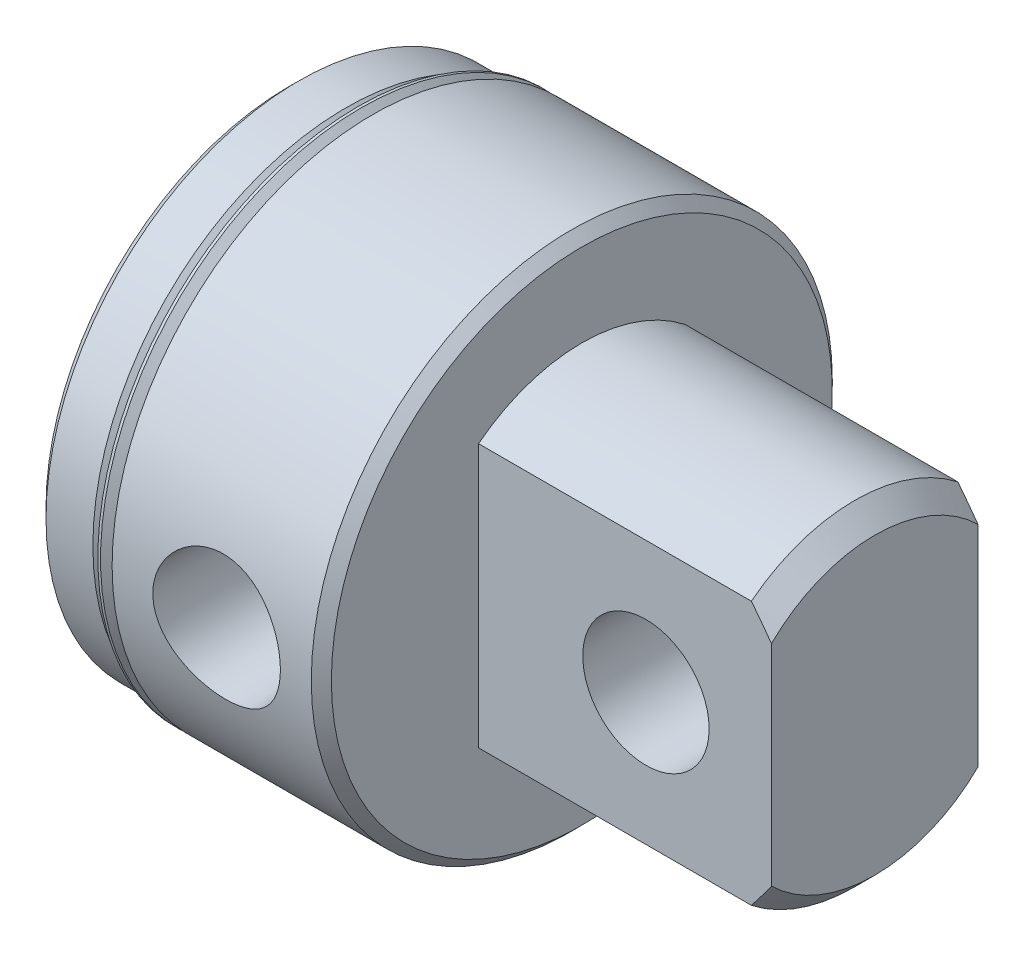
SolidWorks part; units mm, degrees
material "Plain Carbon Steel"
ref_plane "Front Plane" through (0, 0, 0) normal (0, 0, 1) x (1, 0, 0)
ref_plane "Top Plane" through (0, 0, 0) normal (0, 1, 0) x (1, 0, 0)
ref_plane "Right Plane" through (0, 0, 0) normal (1, 0, 0) x (0, 0, -1)
ref_plane "Plane1" through (44.45, 0, 0) normal (1, 0, 0) x (0, 0, -1)
sketch "Sketch1" plane through (0, 0, 0) normal (0, 0, 1) x (1, 0, 0)
  line L0 (0, 0) -> (0, 18.434)
  line L1 (0, 18.434) -> (0.762, 19.196)
  line L2 (0.762, 19.196) -> (4.318, 19.196)
  line L3 (4.318, 19.196) -> (5.334, 18.1801)
  line L4 (5.334, 18.1801) -> (6.35, 18.1801)
  line L5 (6.35, 18.1801) -> (6.35, 19.7676)
  line L6 (6.35, 19.7676) -> (21.463, 19.7676)
  line L7 (21.463, 19.7676) -> (22.225, 19.0055)
  line L8 (22.225, 19.0055) -> (22.225, 0)
  line L9 (22.225, 0) -> (0, 0)
  line L10 (22.225, 0) -> (0, 0) construction
revolve "Revolve1" add sketch "Sketch1" angle 360 about L10 reverse direction yes
sketch "Sketch2" plane through (0, 0, 0) normal (0, 0, 1) x (1, 0, 0)
  line L0 (22.225, 0) -> (22.225, 12.7)
  line L1 (22.225, 12.7) -> (42.926, 12.7)
  line L2 (42.926, 12.7) -> (44.45, 11.176)
  line L3 (44.45, 11.176) -> (44.45, 0)
  line L4 (44.45, 0) -> (22.225, 0)
  line L5 (44.45, 0) -> (22.225, 0) construction
revolve "Revolve2" add sketch "Sketch2" angle 360 about L5 reverse direction yes
sketch "Sketch3" plane through (44.45, 0, 0) normal (1, 0, 0) x (0, 0, -1)
  line L0 (-39.5351, -79.0702) -> (39.5351, -79.0702)
  line L1 (39.5351, -79.0702) -> (39.5351, 79.0702)
  line L2 (39.5351, 79.0702) -> (-39.5351, 79.0702)
  line L3 (-39.5351, 79.0702) -> (-39.5351, -79.0702)
  line L4 (-7.8359, -39.5351) -> (7.8359, -39.5351)
  line L5 (7.8359, -39.5351) -> (7.8359, 39.5351)
  line L6 (7.8359, 39.5351) -> (-7.8359, 39.5351)
  line L7 (-7.8359, 39.5351) -> (-7.8359, -39.5351)
extrude "Cut-Extrude1" cut sketch "Sketch3" against normal blind 22.225
ref_plane "Plane2" through (22.225, 0, 0) normal (1, 0, 0) x (0, 0, -1)
hole_wizard "Hole1" positions "Sketch5" profile "Sketch4" legacy
sketch "Sketch5" plane through (0, 0, 0) normal (-1, 0, 0) x (0, 0, 1)
  point P0 (0, 0)
sketch "Sketch4" plane through (0, 0, 0) normal (0, 1, 0) x (0, 0, 1)
  line L0 (0, 0) -> (0, 24.3529)
  line L1 (0, 24.3529) -> (6.7564, 20.4521)
  line L2 (6.7564, 20.4521) -> (6.7564, 0)
  line L4 (6.7564, 0) -> (0, 0)
  line L6 (0, 24.3529) -> (-6.7564, 20.4521) construction
  line L7 (0, -4.2442) -> (0, 117.3081) construction
  dimension "Diameter" = 13.5128
  dimension "Depth" = 20.4521
  dimension "Drill Angle" = 120
ref_plane "Plane3" through (0, 0, 0) normal (0, 0.9998, 0.0175) x (1, 0, 0)
sketch "Sketch6" plane through (0, 0, 0) normal (0, 0.9998, 0.0175) x (1, 0, 0)
  line L0 (14.2748, 0) -> (18.8978, 0)
  line L1 (18.8978, 0) -> (18.8978, -12.8333)
  line L2 (18.8978, -12.8333) -> (19.1143, -19.7675)
  line L3 (19.1143, -19.7675) -> (14.2748, -19.7675)
  line L4 (14.2748, -19.7675) -> (14.2748, 0)
  line L5 (14.2748, -19.7675) -> (14.2748, 0) construction
revolve "Cut-Revolve1" cut sketch "Sketch6" angle 360 about L5 reverse direction yes
cosmetic thread "Cosmetic Thread1" parameters "D1"=6.9342, "D2"=10.287
ref_plane "Plane4" through (14.2748, 0, 0) normal (1, 0, 0) x (0, 0, -1)
sketch "Sketch7" plane through (0, 0, 0) normal (0, 0, 1) x (1, 0, 0)
  line L0 (0, 0) -> (0, 12.3063)
  line L1 (0, 12.3063) -> (6.35, 12.3063)
  line L2 (6.35, 12.3063) -> (6.35, 0)
  line L3 (6.35, 0) -> (0, 0)
  line L4 (6.35, 0) -> (0, 0) construction
revolve "Cut-Revolve2" cut sketch "Sketch7" angle 360 about L4 reverse direction yes
ref_plane "Plane5" through (5.334, 0, 0) normal (1, 0, 0) x (0, 0, -1)
sketch "Sketch8" plane through (0, 0, 0) normal (0, 0, 1) x (1, 0, 0)
  line L0 (5.2675, 19.6834) -> (6.2166, 18.7343)
  line L1 (6.2166, 18.5547) -> (5.842, 18.1801)
  line L2 (5.842, 18.1801) -> (5.334, 18.1801)
  line L3 (5.334, 18.1801) -> (5.334, 17.9261)
  line L4 (5.334, 17.9261) -> (6.35, 17.9261)
  line L5 (6.35, 17.9261) -> (6.35, 18.8883)
  line L6 (6.35, 18.8883) -> (5.4707, 19.7676)
  line L7 (5.4707, 19.7676) -> (5.2675, 19.7676)
  line L8 (5.2675, 19.7676) -> (5.2675, 19.6834)
  line L9 (6.35, 0) -> (5.334, 0) construction
  arc A0 (6.2166, 18.7343) -> (6.2166, 18.5547) centre (6.1268, 18.6445) cw
revolve "Revolve3" add sketch "Sketch8" angle 360 about L9 reverse direction yes
ref_plane "Plane6" through (44.577, 0, 0) normal (1, 0, 0) x (0, 0, -1)
sketch "Sketch9" plane through (0, 0, 0) normal (0, 0, 1) x (1, 0, 0)
  circle A0 centre (34.925, 0) radius 4.7942
extrude "Cut-Extrude2" cut sketch "Sketch9" along normal blind 11.7538 and the other way blind 11.7538
ref_plane "Plane7" through (0, 0, 0) normal (1, 0, 0) x (0, 0, -1)
ref_plane "Plane8" through (38.1, 0, 0) normal (1, 0, 0) x (0, 0, -1)
ref_plane "Plane9" through (34.925, 0, 0) normal (1, 0, 0) x (0, 0, -1)
ref_plane "Plane10" through (44.45, 0, 0) normal (1, 0, 0) x (0, 0, -1)
ref_plane "Plane11" through (0, 0, 0) normal (0, 0, 1) x (1, 0, 0)
ref_plane "Plane12" through (0, 0, 0) normal (0, 1, 0) x (1, 0, 0)
ref_plane "Plane13" through (0, 14.2875, 0) normal (0, 1, 0) x (1, 0, 0)
ref_plane "Plane14" through (0, 0, 0) normal (0, 0, 1) x (1, 0, 0)
ref_plane "Plane15" through (22.225, 0, 0) normal (1, 0, 0) x (0, 0, -1)
ref_plane "f XY" through (0, 0, 0) normal (0, 0, 1) x (1, 0, 0)
ref_plane "f XZ" through (0, 0, 0) normal (0, -1, 0) x (-1, 0, 0)
ref_plane "f YZ" through (22.225, 0, 0) normal (1, 0, 0) x (0, 0, -1)
ref_axis "f X" through (-80.9, 0, 0) along (1, 0, 0)
ref_axis "f Y" through (22.225, -50, 0) along (0, 1, 0)
ref_axis "f Z" through (22.225, 0, 80.9) along (0, 0, -1)
sketch3d "f"
  point P0 (22.225, 0, 0)
ref_plane "lovra1 XY" through (38.1, 0, 0) normal (1, 0, 0) x (0, 0, -1)
ref_plane "lovra1 XZ" through (0, 0, 0) normal (0, -1, 0) x (-1, 0, 0)
ref_plane "lovra1 YZ" through (0, 0, 0) normal (0, 0, -1) x (-1, 0, 0)
ref_axis "lovra1 X" through (38.1, 0, 80.9) along (0, 0, -1)
ref_axis "lovra1 Y" through (38.1, -50, 0) along (0, 1, 0)
ref_axis "lovra1 Z" through (80.9, 0, 0) along (-1, 0, 0)
sketch3d "lovra1"
  point P0 (38.1, 0, 0)
ref_plane "lovra2 XY" through (38.1, 0, 0) normal (1, 0, 0) x (0, 0, -1)
ref_plane "lovra2 XZ" through (0, 11.049, 0) normal (0, -1, 0) x (-1, 0, 0)
ref_plane "lovra2 YZ" through (0, 0, 0) normal (0, 0, -1) x (-1, 0, 0)
ref_axis "lovra2 X" through (38.1, 11.049, 80.9) along (0, 0, -1)
ref_axis "lovra2 Y" through (38.1, -50, 0) along (0, 1, 0)
ref_axis "lovra2 Z" through (80.9, 11.049, 0) along (-1, 0, 0)
sketch3d "lovra2"
  point P0 (38.1, 11.049, 0)
ref_plane "lovra21 XY" through (0, 0, 0) normal (1, 0, 0) x (0, 0, -1)
ref_plane "lovra21 XZ" through (0, 0, 0) normal (0, -1, 0) x (-1, 0, 0)
ref_plane "lovra21 YZ" through (0, 0, 5.2705) normal (0, 0, -1) x (-1, 0, 0)
ref_axis "lovra21 X" through (0, 0, 80.9) along (0, 0, -1)
ref_axis "lovra21 Y" through (0, -50, 5.2705) along (0, 1, 0)
ref_axis "lovra21 Z" through (80.9, 0, 5.2705) along (-1, 0, 0)
sketch3d "lovra21"
  point P0 (0, 0, 5.2705)
ref_plane "lovra22 XY" through (0, 0, 0) normal (1, 0, 0) x (0, 0, -1)
ref_plane "lovra22 XZ" through (0, 0, 0) normal (0, -1, 0) x (-1, 0, 0)
ref_plane "lovra22 YZ" through (0, 0, -5.2705) normal (0, 0, -1) x (-1, 0, 0)
ref_axis "lovra22 X" through (0, 0, 80.9) along (0, 0, -1)
ref_axis "lovra22 Y" through (0, -50, -5.2705) along (0, 1, 0)
ref_axis "lovra22 Z" through (80.9, 0, -5.2705) along (-1, 0, 0)
sketch3d "lovra22"
  point P0 (0, 0, -5.2705)
ref_plane "lovra3 XY" through (38.1, 0, 0) normal (1, 0, 0) x (0, 0, -1)
ref_plane "lovra3 XZ" through (0, -11.049, 0) normal (0, -1, 0) x (-1, 0, 0)
ref_plane "lovra3 YZ" through (0, 0, 0) normal (0, 0, -1) x (-1, 0, 0)
ref_axis "lovra3 X" through (38.1, -11.049, 80.9) along (0, 0, -1)
ref_axis "lovra3 Y" through (38.1, -50, 0) along (0, 1, 0)
ref_axis "lovra3 Z" through (80.9, -11.049, 0) along (-1, 0, 0)
sketch3d "lovra3"
  point P0 (38.1, -11.049, 0)
ref_plane "olen XY" through (34.925, 0, 0) normal (1, 0, 0) x (0, 0, -1)
ref_plane "olen XZ" through (0, 0, 0) normal (0, -1, 0) x (-1, 0, 0)
ref_plane "olen YZ" through (0, 0, 0) normal (0, 0, -1) x (-1, 0, 0)
ref_axis "olen X" through (34.925, 0, 80.9) along (0, 0, -1)
ref_axis "olen Y" through (34.925, -50, 0) along (0, 1, 0)
ref_axis "olen Z" through (80.9, 0, 0) along (-1, 0, 0)
sketch3d "olen"
  point P0 (34.925, 0, 0)
ref_plane "p1 XY" through (44.45, 0, 0) normal (1, 0, 0) x (0, 0, -1)
ref_plane "p1 XZ" through (0, 0, 0) normal (0, -1, 0) x (-1, 0, 0)
ref_plane "p1 YZ" through (0, 0, 7.8359) normal (0, 0, -1) x (-1, 0, 0)
ref_axis "p1 X" through (44.45, 0, 80.9) along (0, 0, -1)
ref_axis "p1 Y" through (44.45, -50, 7.8359) along (0, 1, 0)
ref_axis "p1 Z" through (80.9, 0, 7.8359) along (-1, 0, 0)
sketch3d "p1"
  point P0 (44.45, 0, 7.8359)
ref_plane "p2 XY" through (44.45, 0, 0) normal (1, 0, 0) x (0, 0, -1)
ref_plane "p2 XZ" through (0, 0, 0) normal (0, -1, 0) x (-1, 0, 0)
ref_plane "p2 YZ" through (0, 0, -7.8359) normal (0, 0, -1) x (-1, 0, 0)
ref_axis "p2 X" through (44.45, 0, 80.9) along (0, 0, -1)
ref_axis "p2 Y" through (44.45, -50, -7.8359) along (0, 1, 0)
ref_axis "p2 Z" through (80.9, 0, -7.8359) along (-1, 0, 0)
sketch3d "p2"
  point P0 (44.45, 0, -7.8359)
ref_plane "port XY" through (0, 0, 0) normal (0, 0, 1) x (1, 0, 0)
ref_plane "port XZ" through (0, 0, 0) normal (0, -1, 0) x (-1, 0, 0)
ref_plane "port YZ" through (14.2748, 0, 0) normal (1, 0, 0) x (0, 0, -1)
ref_axis "port X" through (-80.9, 0, 0) along (1, 0, 0)
ref_axis "port Y" through (14.2748, -50, 0) along (0, 1, 0)
ref_axis "port Z" through (14.2748, 0, 80.9) along (0, 0, -1)
sketch3d "port"
  point P0 (14.2748, 0, 0)
ref_plane "port2 XY" through (44.45, 0, 0) normal (1, 0, 0) x (0, 0, -1)
ref_plane "port2 XZ" through (0, 0, 0) normal (0, -1, 0) x (-1, 0, 0)
ref_plane "port2 YZ" through (0, 0, 0) normal (0, 0, -1) x (-1, 0, 0)
ref_axis "port2 X" through (44.45, 0, 80.9) along (0, 0, -1)
ref_axis "port2 Y" through (44.45, -50, 0) along (0, 1, 0)
ref_axis "port2 Z" through (80.9, 0, 0) along (-1, 0, 0)
sketch3d "port2"
  point P0 (44.45, 0, 0)
ref_plane "thd1 XY" through (44.45, 0, 0) normal (1, 0, 0) x (0, 0, -1)
ref_plane "thd1 XZ" through (0, 0, 0) normal (0, -1, 0) x (-1, 0, 0)
ref_plane "thd1 YZ" through (0, 0, 0) normal (0, 0, -1) x (-1, 0, 0)
ref_axis "thd1 X" through (44.45, 0, 80.9) along (0, 0, -1)
ref_axis "thd1 Y" through (44.45, -50, 0) along (0, 1, 0)
ref_axis "thd1 Z" through (80.9, 0, 0) along (-1, 0, 0)
sketch3d "thd1"
  point P0 (44.45, 0, 0)
ref_plane "thd2 XY" through (44.45, 0, 0) normal (1, 0, 0) x (0, 0, -1)
ref_plane "thd2 XZ" through (0, 0, 0) normal (0, -1, 0) x (-1, 0, 0)
ref_plane "thd2 YZ" through (0, 0, 0) normal (0, 0, -1) x (-1, 0, 0)
ref_axis "thd2 X" through (44.45, 0, 80.9) along (0, 0, -1)
ref_axis "thd2 Y" through (44.45, -50, 0) along (0, 1, 0)
ref_axis "thd2 Z" through (80.9, 0, 0) along (-1, 0, 0)
sketch3d "thd2"
  point P0 (44.45, 0, 0)
ref_plane "to_mounting_bracket XY" through (22.225, 0, 0) normal (1, 0, 0) x (0, 0, -1)
ref_plane "to_mounting_bracket XZ" through (0, 0, 0) normal (0, -1, 0) x (-1, 0, 0)
ref_plane "to_mounting_bracket YZ" through (0, 0, 0) normal (0, 0, -1) x (-1, 0, 0)
ref_axis "to_mounting_bracket X" through (22.225, 0, 80.9) along (0, 0, -1)
ref_axis "to_mounting_bracket Y" through (22.225, -50, 0) along (0, 1, 0)
ref_axis "to_mounting_bracket Z" through (80.9, 0, 0) along (-1, 0, 0)
sketch3d "to_mounting_bracket"
  point P0 (22.225, 0, 0)
ref_plane "to_nut XY" through (0, 0, 0) normal (1, 0, 0) x (0, 0, -1)
ref_plane "to_nut XZ" through (0, 0, 0) normal (0, -1, 0) x (-1, 0, 0)
ref_plane "to_nut YZ" through (0, 0, 0) normal (0, 0, -1) x (-1, 0, 0)
ref_axis "to_nut X" through (0, 0, 80.9) along (0, 0, -1)
ref_axis "to_nut Y" through (0, -50, 0) along (0, 1, 0)
ref_axis "to_nut Z" through (80.9, 0, 0) along (-1, 0, 0)
sketch3d "to_nut"
  point P0 (0, 0, 0)
ref_plane "to_pin XY" through (0, 0, 0) normal (0, 0, 1) x (1, 0, 0)
ref_plane "to_pin XZ" through (0, 0, 0) normal (0, -1, 0) x (-1, 0, 0)
ref_plane "to_pin YZ" through (34.925, 0, 0) normal (1, 0, 0) x (0, 0, -1)
ref_axis "to_pin X" through (-80.9, 0, 0) along (1, 0, 0)
ref_axis "to_pin Y" through (34.925, -50, 0) along (0, 1, 0)
ref_axis "to_pin Z" through (34.925, 0, 80.9) along (0, 0, -1)
sketch3d "to_pin"
  point P0 (34.925, 0, 0)
ref_plane "to_screw XY" through (0, 14.2875, 0) normal (0, 1, 0) x (1, 0, 0)
ref_plane "to_screw XZ" through (0, 0, -10.0838) normal (0, 0, 1) x (1, 0, 0)
ref_plane "to_screw YZ" through (14.2748, 0, 0) normal (1, 0, 0) x (0, 0, -1)
ref_axis "to_screw X" through (-80.9, 14.2875, -10.0838) along (1, 0, 0)
ref_axis "to_screw Y" through (14.2748, 14.2875, 50) along (0, 0, -1)
ref_axis "to_screw Z" through (14.2748, 50, -10.0838) along (0, -1, 0)
sketch3d "to_screw"
  point P0 (14.2748, 14.2875, -10.0838)
ref_plane "to_tube XY" through (5.334, 0, 0) normal (1, 0, 0) x (0, 0, -1)
ref_plane "to_tube XZ" through (0, 0, 0) normal (0, -1, 0) x (-1, 0, 0)
ref_plane "to_tube YZ" through (0, 0, 0) normal (0, 0, -1) x (-1, 0, 0)
ref_axis "to_tube X" through (5.334, 0, 80.9) along (0, 0, -1)
ref_axis "to_tube Y" through (5.334, -50, 0) along (0, 1, 0)
ref_axis "to_tube Z" through (80.9, 0, 0) along (-1, 0, 0)
sketch3d "to_tube"
  point P0 (5.334, 0, 0)
